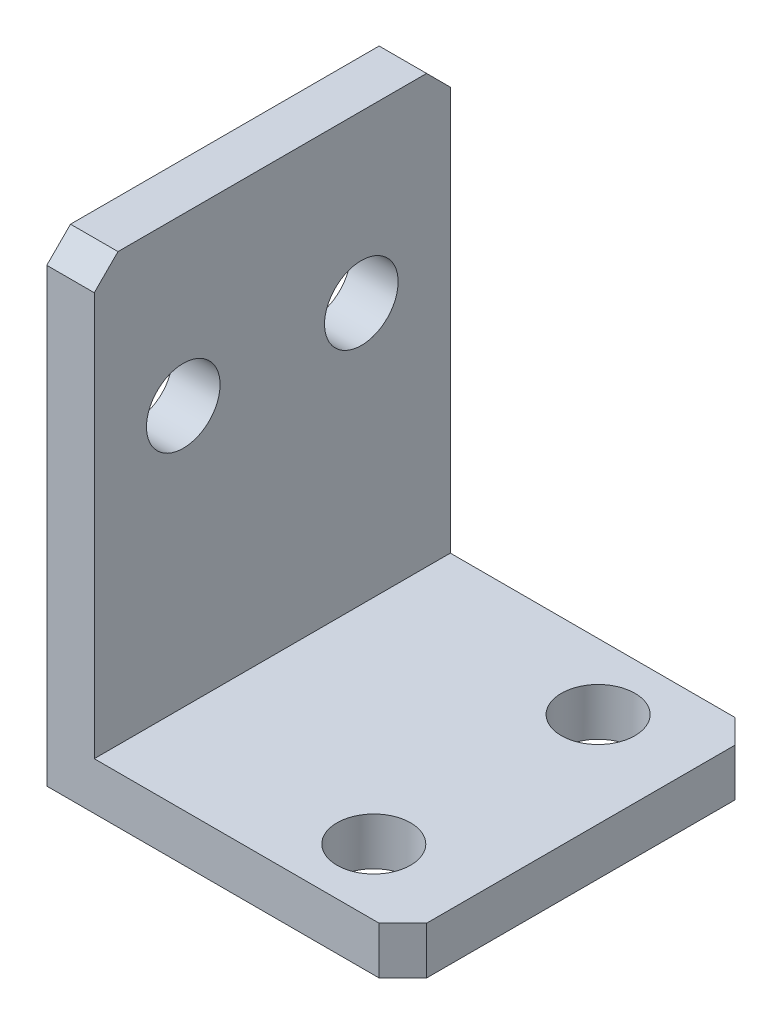
SolidWorks part; units mm, degrees
material "6061 Alloy"
ref_plane "Front Plane" through (0, 0, 0) normal (0, 0, 1) x (1, 0, 0)
ref_plane "Top Plane" through (0, 0, 0) normal (0, 1, 0) x (1, 0, 0)
ref_plane "Right Plane" through (0, 0, 0) normal (1, 0, 0) x (0, 0, -1)
sketch "Sketch1" plane through (0, 0, 0) normal (0, 0, 1) x (1, 0, 0)
  line L0 (0, 0) -> (0, 20)
  line L1 (0, 20) -> (2, 20)
  line L2 (2, 20) -> (2, 2)
  line L3 (2, 2) -> (15, 2)
  line L4 (15, 2) -> (15, 0)
  line L5 (15, 0) -> (0, 0)
  dimension "D1" = 15
  dimension "D2" = 20
  dimension "D3" = 2
extrude "Body" add sketch "Sketch1" along normal blind 15
sketch "Sketch2" plane through (2, 0, 0) normal (1, 0, 0) x (0, 0, -1)
  line L0 (-15, 20) -> (0, 20) construction
  line L1 (-7.5, 20) -> (-7.5, 15.9172) construction
  line L2 (-15, 0) -> (0, 0) construction
  circle A0 centre (-11.25, 13) radius 1.55
  circle A1 centre (-3.75, 13) radius 1.55
  dimension "D3" = 7.5
  dimension "D4" = 13
extrude "ForCarriage" cut sketch "Sketch2" against normal up to surface (2 mm away) up to face at (0, 10, 7.5)
sketch "Sketch3" plane through (0, 2, 0) normal (0, 1, 0) x (1, 0, 0)
  line L0 (15, -7.5) -> (7.2009, -7.5) construction
  line L1 (15, -15) -> (15, 0) construction
  line L2 (0, -15) -> (0, 0) construction
  circle A0 centre (11, -2.775) radius 1.55
  circle A1 centre (11, -12.225) radius 1.55
  dimension "D1" = 3.1
  dimension "D3" = 9.45
  dimension "D4" = 11
extrude "ForSensor" cut sketch "Sketch3" against normal up to surface (2 mm away) up to face at (7.5, 0, 7.5)
chamfer "Chamfer1" distance 1 angle 45 4 edges at (15, 1, 0) (15, 1, 15) (1, 20, 0) (1, 20, 15)
equation "\"D1@Sketch3\"=\"D1@Sketch2\""
